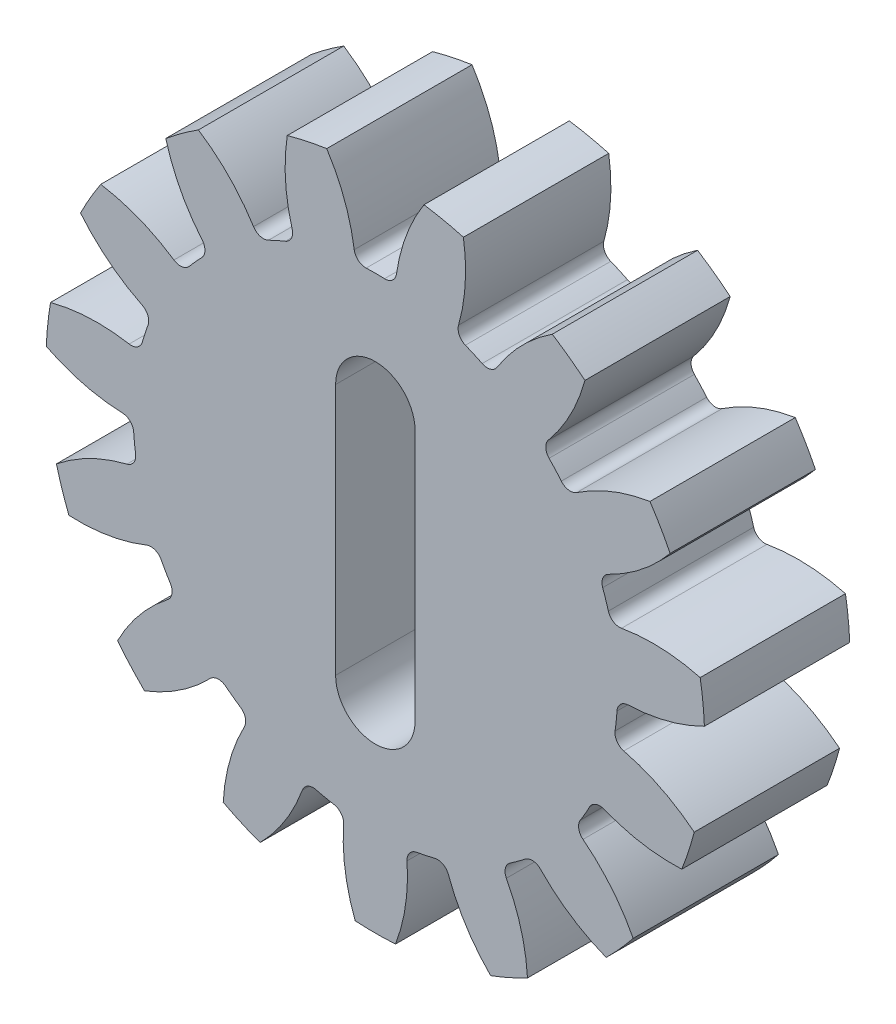
SolidWorks part; units mm, degrees
material "1023 Carbon Steel Sheet (SS)"
ref_plane "Front Plane" through (0, 0, 0) normal (0, 0, 1) x (1, 0, 0)
ref_plane "Top Plane" through (0, 0, 0) normal (0, 1, 0) x (1, 0, 0)
ref_plane "Right Plane" through (0, 0, 0) normal (1, 0, 0) x (0, 0, -1)
sketch "skBase" plane through (0, 0, 0) normal (0, 0, 1) x (1, 0, 0)
  circle A0 centre (0, 0) radius 15
  circle A1 centre (0, 0) radius 17
  circle A2 centre (0, 0) radius 12.5
  dimension "D1" = 30
  dimension "D3" = 4.5
extrude "Base" add sketch "skBase" along normal mid plane 7.5 contours A1
sketch "skToothProfile" plane through (0, 0, 0) normal (0, 0, 1) x (1, 0, 0)
  line L0 (0, 0) -> (0, 17) construction
  line L1 (-1.5679, 14.9178) -> (1.5679, 14.9178) construction
  line L2 (-1.0288, 12.4576) -> (0, 0) construction
  line L3 (0, 10.61) -> (-2.62, 17.8083) construction
  line L4 (0, 0) -> (3.5345, 16.6285) construction
  line L5 (1.5679, 14.9178) -> (4.6353, 14.2658) construction
  circle A0 centre (0, 0) radius 17 construction
  arc A1 (-1.0288, 12.4576) -> (-3.1723, 17.7183) centre (-10.4694, 11.678) ccw
  arc A2 (1.0288, 12.4576) -> (3.1723, 17.7183) centre (10.4694, 11.678) cw
  circle A3 centre (0, 0) radius 12.5 construction
  arc A4 (1.0288, 12.4576) -> (-1.0288, 12.4576) centre (0, 0) ccw
  circle A5 centre (0, 0) radius 15 construction
  circle A6 centre (0, 0) radius 17 construction
  circle A7 centre (0, 0) radius 18
  arc A8 (3.1723, 17.7183) -> (-3.1723, 17.7183) centre (0, 0) ccw
  dimension "D2" = 20
  dimension "D3" = 12
extrude "ToothProfile" cut sketch "skToothProfile" against normal through all and the other way through all
fillet "FilletToothProfile" radius 0.6 2 edges at (1.0288, 12.4576, 0) (-1.0288, 12.4576, 0)
fillet "Fillet1" [suppressed] radius 0.75
pattern_circular "CirPatternTeeth" count 15 over 360 about axis through (0, 0, 3.75) along (0, 0, 1) of "ToothProfile", "FilletToothProfile", "Fillet1"
sketch "skChaveta" plane through (0, 0, 3.75) normal (0, 0, 1) x (1, 0, 0)
  line L0 (0, 1.25) -> (0, 0) construction
  circle A0 centre (0, 0) radius 1.25
  dimension "D1" = 2.5
sketch "skRebaixo" plane through (0, 0, 3.75) normal (0, 0, 1) x (1, 0, 0)
  circle A0 centre (0, 0) radius 21.5
  circle A1 centre (0, 0) radius 7.5
  dimension "D1" = 43
  dimension "D2" = 15
sketch "Sketch4" plane through (0, 0, -3.75) normal (0, 0, -1) x (-1, 0, 0)
  circle A0 centre (0, 0) radius 17.5
  arc A2 (0.4735, 12.491) -> (-0.4735, 12.491) centre (0, 0) ccw
  arc A3 (0.4735, 12.491) -> (-0.4735, 12.491) centre (0, 0) ccw
  arc A63 (-2.5097, 16.8137) -> (-4.546, 16.3809) centre (0, 0) ccw
  arc A64 (-2.5097, 16.8137) -> (-4.546, 16.3809) centre (0, 0) ccw
  arc A67 (-16.4593, -4.2535) -> (-15.816, -6.2334) centre (0, 0) ccw
  arc A68 (-16.4593, -4.2535) -> (-15.816, -6.2334) centre (0, 0) ccw
  arc A69 (-13.3063, -10.5803) -> (-11.9132, -12.1274) centre (0, 0) ccw
  arc A70 (-13.3063, -10.5803) -> (-11.9132, -12.1274) centre (0, 0) ccw
  arc A71 (-7.8525, -15.0778) -> (-5.9506, -15.9245) centre (0, 0) ccw
  arc A72 (-7.8525, -15.0778) -> (-5.9506, -15.9245) centre (0, 0) ccw
  arc A73 (-1.0409, -16.9681) -> (1.0409, -16.9681) centre (0, 0) ccw
  arc A74 (-1.0409, -16.9681) -> (1.0409, -16.9681) centre (0, 0) ccw
  arc A75 (5.9506, -15.9245) -> (7.8525, -15.0778) centre (0, 0) ccw
  arc A76 (5.9506, -15.9245) -> (7.8525, -15.0778) centre (0, 0) ccw
  arc A77 (11.9132, -12.1274) -> (13.3063, -10.5803) centre (0, 0) ccw
  arc A78 (11.9132, -12.1274) -> (13.3063, -10.5803) centre (0, 0) ccw
  arc A79 (15.816, -6.2334) -> (16.4593, -4.2535) centre (0, 0) ccw
  arc A80 (15.816, -6.2334) -> (16.4593, -4.2535) centre (0, 0) ccw
  arc A81 (16.984, 0.7384) -> (16.7663, 2.8089) centre (0, 0) ccw
  arc A82 (16.984, 0.7384) -> (16.7663, 2.8089) centre (0, 0) ccw
  arc A83 (-11.9132, -12.1274) -> (-8.527, -9.8816) centre (-15.3341, -3.2939) ccw
  arc A84 (-11.9132, -12.1274) -> (-8.527, -9.8816) centre (-15.3341, -3.2939) ccw
  arc A85 (-7.7251, -9.8272) -> (-8.527, -9.8816) centre (-8.0959, -10.2989) ccw
  arc A86 (-7.7251, -9.8272) -> (-8.527, -9.8816) centre (-8.0959, -10.2989) ccw
  arc A87 (-7.7251, -9.8272) -> (-6.959, -10.3838) centre (0, 0) ccw
  arc A88 (-7.7251, -9.8272) -> (-6.959, -10.3838) centre (0, 0) ccw
  arc A89 (-6.763, -11.1633) -> (-6.959, -10.3838) centre (-7.293, -10.8822) ccw
  arc A90 (-6.763, -11.1633) -> (-6.959, -10.3838) centre (-7.293, -10.8822) ccw
  arc A91 (-6.763, -11.1633) -> (-7.8525, -15.0778) centre (1.6058, -15.6014) ccw
  arc A92 (-6.763, -11.1633) -> (-7.8525, -15.0778) centre (1.6058, -15.6014) ccw
  arc A93 (-5.9506, -15.9245) -> (-3.7706, -12.4956) centre (-12.6686, -9.2461) ccw
  arc A94 (-5.9506, -15.9245) -> (-3.7706, -12.4956) centre (-12.6686, -9.2461) ccw
  arc A95 (-3.0602, -12.1196) -> (-3.7706, -12.4956) centre (-3.207, -12.7014) ccw
  arc A96 (-3.0602, -12.1196) -> (-3.7706, -12.4956) centre (-3.207, -12.7014) ccw
  arc A97 (-3.0602, -12.1196) -> (-2.1339, -12.3165) centre (0, 0) ccw
  arc A98 (-3.0602, -12.1196) -> (-2.1339, -12.3165) centre (0, 0) ccw
  arc A99 (-1.6377, -12.9489) -> (-2.1339, -12.3165) centre (-2.2363, -12.9077) ccw
  arc A100 (-1.6377, -12.9489) -> (-2.1339, -12.3165) centre (-2.2363, -12.9077) ccw
  arc A101 (-1.6377, -12.9489) -> (-1.0409, -16.9681) centre (7.8126, -13.5995) ccw
  arc A102 (-1.6377, -12.9489) -> (-1.0409, -16.9681) centre (7.8126, -13.5995) ccw
  arc A103 (1.0409, -16.9681) -> (1.6377, -12.9489) centre (-7.8126, -13.5995) ccw
  arc A104 (1.0409, -16.9681) -> (1.6377, -12.9489) centre (-7.8126, -13.5995) ccw
  arc A105 (2.1339, -12.3165) -> (1.6377, -12.9489) centre (2.2363, -12.9077) ccw
  arc A106 (2.1339, -12.3165) -> (1.6377, -12.9489) centre (2.2363, -12.9077) ccw
  arc A107 (2.1339, -12.3165) -> (3.0602, -12.1196) centre (0, 0) ccw
  arc A108 (2.1339, -12.3165) -> (3.0602, -12.1196) centre (0, 0) ccw
  arc A109 (3.7706, -12.4956) -> (3.0602, -12.1196) centre (3.207, -12.7014) ccw
  arc A110 (3.7706, -12.4956) -> (3.0602, -12.1196) centre (3.207, -12.7014) ccw
  arc A111 (3.7706, -12.4956) -> (5.9506, -15.9245) centre (12.6686, -9.2461) ccw
  arc A112 (3.7706, -12.4956) -> (5.9506, -15.9245) centre (12.6686, -9.2461) ccw
  arc A113 (7.8525, -15.0778) -> (6.763, -11.1633) centre (-1.6058, -15.6014) ccw
  arc A114 (7.8525, -15.0778) -> (6.763, -11.1633) centre (-1.6058, -15.6014) ccw
  arc A115 (6.959, -10.3838) -> (6.763, -11.1633) centre (7.293, -10.8822) ccw
  arc A116 (6.959, -10.3838) -> (6.763, -11.1633) centre (7.293, -10.8822) ccw
  arc A117 (6.959, -10.3838) -> (7.7251, -9.8272) centre (0, 0) ccw
  arc A118 (6.959, -10.3838) -> (7.7251, -9.8272) centre (0, 0) ccw
  arc A119 (8.527, -9.8816) -> (7.7251, -9.8272) centre (8.0959, -10.2989) ccw
  arc A120 (8.527, -9.8816) -> (7.7251, -9.8272) centre (8.0959, -10.2989) ccw
  arc A121 (8.527, -9.8816) -> (11.9132, -12.1274) centre (15.3341, -3.2939) ccw
  arc A122 (8.527, -9.8816) -> (11.9132, -12.1274) centre (15.3341, -3.2939) ccw
  arc A123 (13.3063, -10.5803) -> (10.7188, -7.4474) centre (4.8787, -14.9057) ccw
  arc A124 (13.3063, -10.5803) -> (10.7188, -7.4474) centre (4.8787, -14.9057) ccw
  arc A125 (10.5808, -6.6556) -> (10.7188, -7.4474) centre (11.0887, -6.975) ccw
  arc A126 (10.5808, -6.6556) -> (10.7188, -7.4474) centre (11.0887, -6.975) ccw
  arc A127 (10.5808, -6.6556) -> (11.0543, -5.8355) centre (0, 0) ccw
  arc A128 (10.5808, -6.6556) -> (11.0543, -5.8355) centre (0, 0) ccw
  arc A129 (11.8091, -5.559) -> (11.0543, -5.8355) centre (11.5849, -6.1156) ccw
  arc A130 (11.8091, -5.559) -> (11.0543, -5.8355) centre (11.5849, -6.1156) ccw
  arc A131 (11.8091, -5.559) -> (15.816, -6.2334) centre (15.3481, 3.2278) ccw
  arc A132 (11.8091, -5.559) -> (15.816, -6.2334) centre (15.3481, 3.2278) ccw
  arc A133 (16.4593, -4.2535) -> (12.8212, -2.4438) centre (10.5196, -11.6327) ccw
  arc A134 (16.4593, -4.2535) -> (12.8212, -2.4438) centre (10.5196, -11.6327) ccw
  arc A135 (12.3731, -1.7765) -> (12.8212, -2.4438) centre (12.967, -1.8618) ccw
  arc A136 (12.3731, -1.7765) -> (12.8212, -2.4438) centre (12.967, -1.8618) ccw
  arc A137 (12.3731, -1.7765) -> (12.4721, -0.8348) centre (0, 0) ccw
  arc A138 (12.3731, -1.7765) -> (12.4721, -0.8348) centre (0, 0) ccw
  arc A139 (13.0492, -0.2752) -> (12.4721, -0.8348) centre (13.0708, -0.8749) ccw
  arc A140 (13.0492, -0.2752) -> (12.4721, -0.8348) centre (13.0708, -0.8749) ccw
  arc A141 (13.0492, -0.2752) -> (16.984, 0.7384) centre (12.7083, 9.1914) ccw
  arc A142 (13.0492, -0.2752) -> (16.984, 0.7384) centre (12.7083, 9.1914) ccw
  arc A143 (16.7663, 2.8089) -> (12.7068, 2.9823) centre (14.3416, -6.3483) ccw
  arc A144 (16.7663, 2.8089) -> (12.7068, 2.9823) centre (14.3416, -6.3483) ccw
  arc A145 (12.026, 3.4096) -> (12.7068, 2.9823) centre (12.6032, 3.5733) ccw
  arc A146 (12.026, 3.4096) -> (12.7068, 2.9823) centre (12.6032, 3.5733) ccw
  arc A147 (12.026, 3.4096) -> (11.7334, 4.3102) centre (0, 0) ccw
  arc A148 (12.026, 3.4096) -> (11.7334, 4.3102) centre (0, 0) ccw
  arc A149 (12.033, 5.0561) -> (11.7334, 4.3102) centre (12.2966, 4.5171) ccw
  arc A150 (12.033, 5.0561) -> (11.7334, 4.3102) centre (12.2966, 4.5171) ccw
  arc A151 (12.033, 5.0561) -> (15.2153, 7.5826) centre (7.8712, 13.5657) ccw
  arc A152 (12.033, 5.0561) -> (15.2153, 7.5826) centre (7.8712, 13.5657) ccw
  arc A153 (14.1743, 9.3855) -> (10.3952, 7.8928) centre (15.6838, 0.0338) ccw
  arc A154 (14.1743, 9.3855) -> (10.3952, 7.8928) centre (15.6838, 0.0338) ccw
  arc A155 (9.5995, 8.0063) -> (10.3952, 7.8928) centre (10.0602, 8.3906) ccw
  arc A156 (9.5995, 8.0063) -> (10.3952, 7.8928) centre (10.0602, 8.3906) ccw
  arc A157 (9.5995, 8.0063) -> (8.9658, 8.71) centre (0, 0) ccw
  arc A158 (9.5995, 8.0063) -> (8.9658, 8.71) centre (0, 0) ccw
  arc A159 (8.9361, 9.5132) -> (8.9658, 8.71) centre (9.3962, 9.1281) ccw
  arc A160 (8.9361, 9.5132) -> (8.9658, 8.71) centre (9.3962, 9.1281) ccw
  arc A161 (8.9361, 9.5132) -> (10.8157, 13.1156) centre (1.673, 15.5944) ccw
  arc A162 (8.9361, 9.5132) -> (10.8157, 13.1156) centre (1.673, 15.5944) ccw
  arc A163 (9.1315, 14.3393) -> (6.2862, 11.4385) centre (14.3141, 6.4101) ccw
  arc A164 (9.1315, 14.3393) -> (6.2862, 11.4385) centre (14.3141, 6.4101) ccw
  arc A165 (5.5131, 11.2185) -> (6.2862, 11.4385) centre (5.7777, 11.757) ccw
  arc A166 (5.5131, 11.2185) -> (6.2862, 11.4385) centre (5.7777, 11.757) ccw
  arc A167 (5.5131, 11.2185) -> (4.648, 11.6037) centre (0, 0) ccw
  arc A168 (5.5131, 11.2185) -> (4.648, 11.6037) centre (0, 0) ccw
  arc A169 (4.2942, 12.3254) -> (4.648, 11.6037) centre (4.8711, 12.1607) ccw
  arc A170 (4.2942, 12.3254) -> (4.648, 11.6037) centre (4.8711, 12.1607) ccw
  arc A171 (4.2942, 12.3254) -> (4.546, 16.3809) centre (-4.8144, 14.9266) ccw
  arc A172 (4.2942, 12.3254) -> (4.546, 16.3809) centre (-4.8144, 14.9266) ccw
  arc A173 (2.5097, 16.8137) -> (1.0903, 13.0065) centre (10.4694, 11.678) ccw
  arc A174 (2.5097, 16.8137) -> (1.0903, 13.0065) centre (10.4694, 11.678) ccw
  arc A175 (0.4735, 12.491) -> (1.0903, 13.0065) centre (0.4962, 13.0906) ccw
  arc A176 (0.4735, 12.491) -> (1.0903, 13.0065) centre (0.4962, 13.0906) ccw
  arc A177 (-1.0903, 13.0065) -> (-0.4735, 12.491) centre (-0.4962, 13.0906) ccw
  arc A178 (-1.0903, 13.0065) -> (-0.4735, 12.491) centre (-0.4962, 13.0906) ccw
  arc A179 (-1.0903, 13.0065) -> (-2.5097, 16.8137) centre (-10.4694, 11.678) ccw
  arc A180 (-1.0903, 13.0065) -> (-2.5097, 16.8137) centre (-10.4694, 11.678) ccw
  arc A199 (15.2153, 7.5826) -> (14.1743, 9.3855) centre (0, 0) ccw
  arc A200 (15.2153, 7.5826) -> (14.1743, 9.3855) centre (0, 0) ccw
  arc A201 (10.8157, 13.1156) -> (9.1315, 14.3393) centre (0, 0) ccw
  arc A202 (10.8157, 13.1156) -> (9.1315, 14.3393) centre (0, 0) ccw
  arc A203 (4.546, 16.3809) -> (2.5097, 16.8137) centre (0, 0) ccw
  arc A204 (4.546, 16.3809) -> (2.5097, 16.8137) centre (0, 0) ccw
  arc A215 (-9.1315, 14.3393) -> (-10.8157, 13.1156) centre (0, 0) ccw
  arc A216 (-9.1315, 14.3393) -> (-10.8157, 13.1156) centre (0, 0) ccw
  arc A217 (-14.1743, 9.3855) -> (-15.2153, 7.5826) centre (0, 0) ccw
  arc A218 (-14.1743, 9.3855) -> (-15.2153, 7.5826) centre (0, 0) ccw
  arc A219 (-16.7663, 2.8089) -> (-16.984, 0.7384) centre (0, 0) ccw
  arc A220 (-16.7663, 2.8089) -> (-16.984, 0.7384) centre (0, 0) ccw
  arc A221 (-12.7068, 2.9823) -> (-16.7663, 2.8089) centre (-14.3416, -6.3483) ccw
  arc A222 (-12.7068, 2.9823) -> (-16.7663, 2.8089) centre (-14.3416, -6.3483) ccw
  arc A223 (-15.2153, 7.5826) -> (-12.033, 5.0561) centre (-7.8712, 13.5657) ccw
  arc A224 (-15.2153, 7.5826) -> (-12.033, 5.0561) centre (-7.8712, 13.5657) ccw
  arc A225 (-11.7334, 4.3102) -> (-12.033, 5.0561) centre (-12.2966, 4.5171) ccw
  arc A226 (-11.7334, 4.3102) -> (-12.033, 5.0561) centre (-12.2966, 4.5171) ccw
  arc A227 (-11.7334, 4.3102) -> (-12.026, 3.4096) centre (0, 0) ccw
  arc A228 (-11.7334, 4.3102) -> (-12.026, 3.4096) centre (0, 0) ccw
  arc A229 (-12.7068, 2.9823) -> (-12.026, 3.4096) centre (-12.6032, 3.5733) ccw
  arc A230 (-12.7068, 2.9823) -> (-12.026, 3.4096) centre (-12.6032, 3.5733) ccw
  arc A231 (-4.546, 16.3809) -> (-4.2942, 12.3254) centre (4.8144, 14.9266) ccw
  arc A232 (-4.546, 16.3809) -> (-4.2942, 12.3254) centre (4.8144, 14.9266) ccw
  arc A233 (-4.648, 11.6037) -> (-4.2942, 12.3254) centre (-4.8711, 12.1607) ccw
  arc A234 (-4.648, 11.6037) -> (-4.2942, 12.3254) centre (-4.8711, 12.1607) ccw
  arc A235 (-4.648, 11.6037) -> (-5.5131, 11.2185) centre (0, 0) ccw
  arc A236 (-4.648, 11.6037) -> (-5.5131, 11.2185) centre (0, 0) ccw
  arc A237 (-6.2862, 11.4385) -> (-5.5131, 11.2185) centre (-5.7777, 11.757) ccw
  arc A238 (-6.2862, 11.4385) -> (-5.5131, 11.2185) centre (-5.7777, 11.757) ccw
  arc A239 (-6.2862, 11.4385) -> (-9.1315, 14.3393) centre (-14.3141, 6.4101) ccw
  arc A240 (-6.2862, 11.4385) -> (-9.1315, 14.3393) centre (-14.3141, 6.4101) ccw
  arc A241 (-10.8157, 13.1156) -> (-8.9361, 9.5132) centre (-1.673, 15.5944) ccw
  arc A242 (-10.8157, 13.1156) -> (-8.9361, 9.5132) centre (-1.673, 15.5944) ccw
  arc A243 (-8.9658, 8.71) -> (-8.9361, 9.5132) centre (-9.3962, 9.1281) ccw
  arc A244 (-8.9658, 8.71) -> (-8.9361, 9.5132) centre (-9.3962, 9.1281) ccw
  arc A245 (-8.9658, 8.71) -> (-9.5995, 8.0063) centre (0, 0) ccw
  arc A246 (-8.9658, 8.71) -> (-9.5995, 8.0063) centre (0, 0) ccw
  arc A247 (-10.3952, 7.8928) -> (-9.5995, 8.0063) centre (-10.0602, 8.3906) ccw
  arc A248 (-10.3952, 7.8928) -> (-9.5995, 8.0063) centre (-10.0602, 8.3906) ccw
  arc A249 (-10.3952, 7.8928) -> (-14.1743, 9.3855) centre (-15.6838, 0.0338) ccw
  arc A250 (-10.3952, 7.8928) -> (-14.1743, 9.3855) centre (-15.6838, 0.0338) ccw
  arc A273 (-16.984, 0.7384) -> (-13.0492, -0.2752) centre (-12.7083, 9.1914) ccw
  arc A274 (-16.984, 0.7384) -> (-13.0492, -0.2752) centre (-12.7083, 9.1914) ccw
  arc A275 (-12.4721, -0.8348) -> (-13.0492, -0.2752) centre (-13.0708, -0.8749) ccw
  arc A276 (-12.4721, -0.8348) -> (-13.0492, -0.2752) centre (-13.0708, -0.8749) ccw
  arc A277 (-12.4721, -0.8348) -> (-12.3731, -1.7765) centre (0, 0) ccw
  arc A278 (-12.4721, -0.8348) -> (-12.3731, -1.7765) centre (0, 0) ccw
  arc A279 (-12.8212, -2.4438) -> (-12.3731, -1.7765) centre (-12.967, -1.8618) ccw
  arc A280 (-12.8212, -2.4438) -> (-12.3731, -1.7765) centre (-12.967, -1.8618) ccw
  arc A281 (-12.8212, -2.4438) -> (-16.4593, -4.2535) centre (-10.5196, -11.6327) ccw
  arc A282 (-12.8212, -2.4438) -> (-16.4593, -4.2535) centre (-10.5196, -11.6327) ccw
  arc A289 (-15.816, -6.2334) -> (-11.8091, -5.559) centre (-15.3481, 3.2278) ccw
  arc A290 (-15.816, -6.2334) -> (-11.8091, -5.559) centre (-15.3481, 3.2278) ccw
  arc A291 (-11.0543, -5.8355) -> (-11.8091, -5.559) centre (-11.5849, -6.1156) ccw
  arc A292 (-11.0543, -5.8355) -> (-11.8091, -5.559) centre (-11.5849, -6.1156) ccw
  arc A293 (-11.0543, -5.8355) -> (-10.5808, -6.6556) centre (0, 0) ccw
  arc A294 (-11.0543, -5.8355) -> (-10.5808, -6.6556) centre (0, 0) ccw
  arc A295 (-10.7188, -7.4474) -> (-10.5808, -6.6556) centre (-11.0887, -6.975) ccw
  arc A296 (-10.7188, -7.4474) -> (-10.5808, -6.6556) centre (-11.0887, -6.975) ccw
  arc A297 (-10.7188, -7.4474) -> (-13.3063, -10.5803) centre (-4.8787, -14.9057) ccw
  arc A298 (-10.7188, -7.4474) -> (-13.3063, -10.5803) centre (-4.8787, -14.9057) ccw
  dimension "D1" = 0
sketch "Sketch5" plane through (0, 0, -3.75) normal (0, 0, -1) x (-1, 0, 0)
  line L0 (0, 6.5) -> (0, -6.5) construction
  line L1 (2.05, 6.5) -> (2.05, -6.5)
  line L2 (-2.05, 6.5) -> (-2.05, -6.5)
  arc A0 (2.05, 6.5) -> (-2.05, 6.5) centre (0, 6.5) ccw
  arc A1 (-2.05, -6.5) -> (2.05, -6.5) centre (0, -6.5) ccw
  point P3 (0, 0)
  dimension "D1" = 2.05
  dimension "D2" = 13
extrude "Cut-Extrude1" cut sketch "Sketch5" against normal through all
equation "\"Module\"= 2mm"
equation "\"Number_Of_Teeth\"= 15"
equation "\"D1@skBase\"=\"Module\" * \"Number_Of_Teeth\""
equation "\"D2@skBase\"=\"Module\""
equation "\"D3@skBase\"=\"Module\" * if( \"Module\" >=1.25, 2.25, 2.4)"
equation "\"Pressure_Angle\"= 20deg"
equation "\"D2@skToothProfile\"=\"Pressure_Angle\""
equation "\"D3@skToothProfile\"=180 / \"Number_Of_Teeth\""
equation "\"D1@FilletToothProfile\"= 0.3 * \"Module\""
equation "\"D1@CirPatternTeeth\"=\"Number_Of_Teeth\""
equation "\"Width\"= 7.5mm"
equation "\"D1@Base\"=\"Width\""
